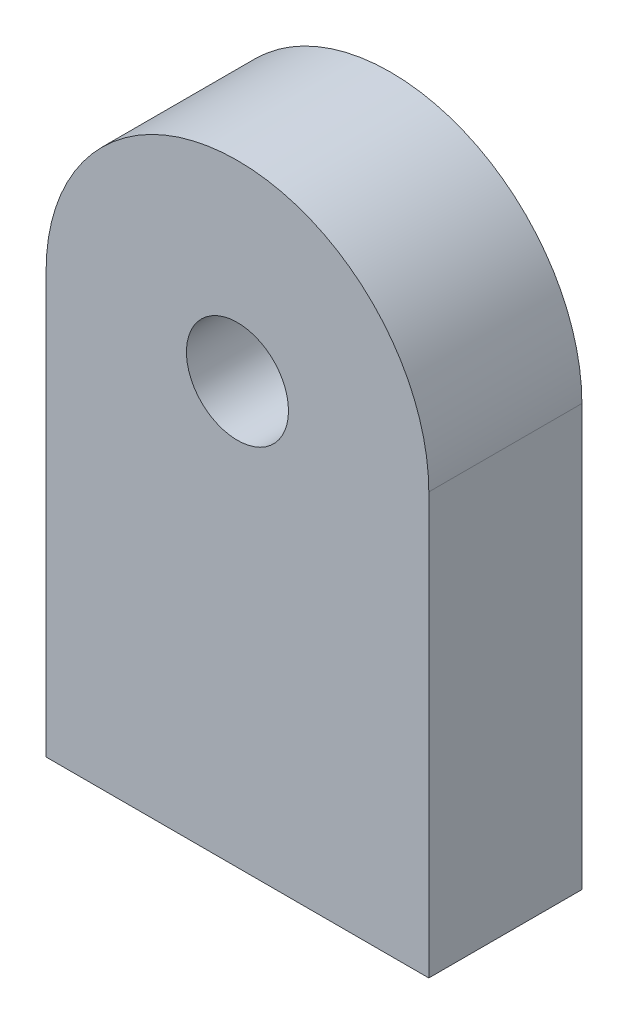
SolidWorks part; units mm, degrees
ref_plane "Front Plane" through (0, 0, 0) normal (0, 0, 1) x (1, 0, 0)
ref_plane "Top Plane" through (0, 0, 0) normal (0, 1, 0) x (1, 0, 0)
ref_plane "Right Plane" through (0, 0, 0) normal (1, 0, 0) x (0, 0, -1)
sketch "Sketch2" plane through (0, 0, 0) normal (0, 0, 1) x (1, 0, 0)
  circle A0 centre (0, 0) radius 15
  circle A1 centre (0, 0) radius 11
  dimension "D1" = 30
  dimension "D2" = 22
extrude "Boss-Extrude1" add sketch "Sketch2" along normal blind 4
sketch "Sketch3" plane through (0, 0, 4) normal (0, 0, 1) x (1, 0, 0)
  circle A0 centre (0, 0) radius 15
  circle A1 centre (0, 0) radius 4
  circle A2 centre (0, 0) radius 15 construction
  dimension "D1" = 8
  dimension "D2" = 0
extrude "Boss-Extrude2" add sketch "Sketch3" along normal blind 8
sketch "Sketch6" plane through (0, 0, 12) normal (0, 0, 1) x (1, 0, 0)
  line L0 (-15, 0) -> (-15, -33)
  line L1 (15, 0) -> (15, -33)
  line L2 (15, -33) -> (-15, -33)
  circle A0 centre (0, 0) radius 15 construction
  circle A2 centre (0, 0) radius 15
  arc A3 (-15, 0) -> (15, 0) centre (0, 0) ccw
  dimension "D1" = 33
  dimension "D2" = 0
extrude "Boss-Extrude5" add sketch "Sketch6" against normal blind 12
